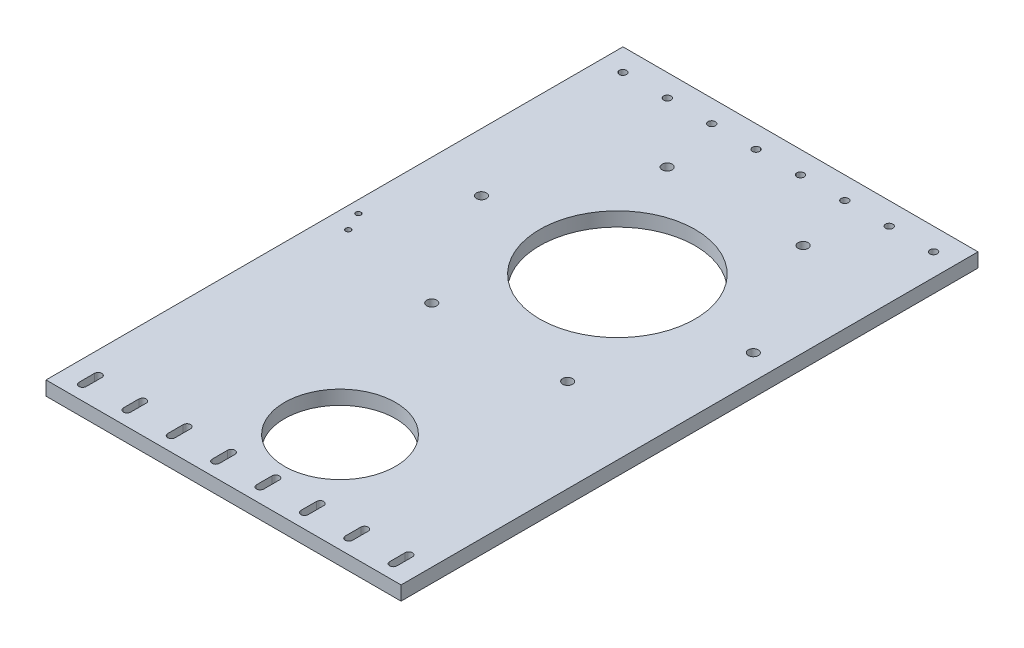
SolidWorks part; units mm, degrees
material "6061 Alloy"
ref_plane "Front Plane" through (0, 0, 0) normal (0, 0, 1) x (1, 0, 0)
ref_plane "Top Plane" through (0, 0, 0) normal (0, 1, 0) x (1, 0, 0)
ref_plane "Right Plane" through (0, 0, 0) normal (1, 0, 0) x (0, 0, -1)
sketch "Sketch1" plane through (0, 0, 0) normal (0, 1, 0) x (1, 0, 0)
  line L0 (87.5, 260) -> (87.5, 0) construction
  line L1 (0, 0) -> (160, 0)
  line L2 (0, 0) -> (0, 260)
  line L3 (0, 260) -> (160, 260)
  line L4 (160, 0) -> (160, 260)
  line L5 (87.5, 170) -> (148.75, 170) construction
  line L6 (10, 6.5) -> (10, 13.5) construction
  line L7 (5.4755, 135.2989) -> (9.5163, 126.7011) construction
  line L8 (22, 0) -> (22, 260) construction
  line L9 (22, 136) -> (0, 136) construction
  line L10 (22, 126) -> (0, 126) construction
  line L11 (0, 136) -> (0, 126) construction
  line L12 (17.3003, 136) -> (22, 126) construction
  line L13 (8.35, 6.5) -> (8.35, 13.5)
  line L14 (11.65, 6.5) -> (11.65, 13.5)
  line L15 (10, 250) -> (10, 0) construction
  line L16 (31.65, 6.5) -> (31.65, 13.5)
  line L17 (28.35, 6.5) -> (28.35, 13.5)
  line L18 (30, 6.5) -> (30, 13.5) construction
  line L19 (51.65, 6.5) -> (51.65, 13.5)
  line L20 (48.35, 6.5) -> (48.35, 13.5)
  line L21 (50, 6.5) -> (50, 13.5) construction
  line L22 (71.65, 6.5) -> (71.65, 13.5)
  line L23 (68.35, 6.5) -> (68.35, 13.5)
  line L24 (70, 6.5) -> (70, 13.5) construction
  line L25 (91.65, 6.5) -> (91.65, 13.5)
  line L26 (88.35, 6.5) -> (88.35, 13.5)
  line L27 (90, 6.5) -> (90, 13.5) construction
  line L28 (111.65, 6.5) -> (111.65, 13.5)
  line L29 (108.35, 6.5) -> (108.35, 13.5)
  line L30 (110, 6.5) -> (110, 13.5) construction
  line L31 (131.65, 6.5) -> (131.65, 13.5)
  line L32 (128.35, 6.5) -> (128.35, 13.5)
  line L33 (130, 6.5) -> (130, 13.5) construction
  line L34 (151.65, 6.5) -> (151.65, 13.5)
  line L35 (148.35, 6.5) -> (148.35, 13.5)
  line L36 (150, 6.5) -> (150, 13.5) construction
  line L37 (10, 250) -> (30, 250) construction
  circle A0 centre (87.5, 170) radius 35
  circle A1 centre (87.5, 45) radius 25
  circle A2 centre (87.5, 170) radius 61.25 construction
  circle A3 centre (148.75, 170) radius 2.25
  circle A4 centre (118.125, 116.9559) radius 2.25
  circle A5 centre (56.875, 116.9559) radius 2.25
  circle A6 centre (26.25, 170) radius 2.25
  circle A7 centre (56.875, 223.0441) radius 2.25
  circle A8 centre (118.125, 223.0441) radius 2.25
  circle A10 centre (5.4755, 135.2989) radius 1.175
  circle A11 centre (9.5163, 126.7011) radius 1.175
  circle A12 centre (87.5, 170) radius 78 construction
  circle A13 centre (10, 250) radius 1.65
  arc A14 (8.35, 6.5) -> (11.65, 6.5) centre (10, 6.5) ccw
  arc A15 (11.65, 13.5) -> (8.35, 13.5) centre (10, 13.5) ccw
  circle A16 centre (30, 250) radius 1.65
  arc A17 (28.35, 6.5) -> (31.65, 6.5) centre (30, 6.5) ccw
  arc A18 (31.65, 13.5) -> (28.35, 13.5) centre (30, 13.5) ccw
  circle A19 centre (50, 250) radius 1.65
  arc A20 (48.35, 6.5) -> (51.65, 6.5) centre (50, 6.5) ccw
  arc A21 (51.65, 13.5) -> (48.35, 13.5) centre (50, 13.5) ccw
  circle A22 centre (70, 250) radius 1.65
  arc A23 (68.35, 6.5) -> (71.65, 6.5) centre (70, 6.5) ccw
  arc A24 (71.65, 13.5) -> (68.35, 13.5) centre (70, 13.5) ccw
  circle A25 centre (90, 250) radius 1.65
  arc A26 (88.35, 6.5) -> (91.65, 6.5) centre (90, 6.5) ccw
  arc A27 (91.65, 13.5) -> (88.35, 13.5) centre (90, 13.5) ccw
  circle A28 centre (110, 250) radius 1.65
  arc A29 (108.35, 6.5) -> (111.65, 6.5) centre (110, 6.5) ccw
  arc A30 (111.65, 13.5) -> (108.35, 13.5) centre (110, 13.5) ccw
  circle A31 centre (130, 250) radius 1.65
  arc A32 (128.35, 6.5) -> (131.65, 6.5) centre (130, 6.5) ccw
  arc A33 (131.65, 13.5) -> (128.35, 13.5) centre (130, 13.5) ccw
  circle A34 centre (150, 250) radius 1.65
  arc A35 (148.35, 6.5) -> (151.65, 6.5) centre (150, 6.5) ccw
  arc A36 (151.65, 13.5) -> (148.35, 13.5) centre (150, 13.5) ccw
  point P15 (87.5, 170)
  point P29 (10, 10)
  point P42 (7.4959, 131)
  point P43 (0, 131)
  point P55 (30, 10)
  point P65 (50, 10)
  point P74 (70, 10)
  point P83 (90, 10)
  point P92 (110, 10)
  point P101 (130, 10)
  point P110 (150, 10)
  dimension "D3" = 70
  dimension "D4" = 50
  dimension "D7" = 122.5
  dimension "D8" = 4.5
  dimension "D11" = 124
  dimension "D13" = 2.35
  dimension "D16" = 156
  dimension "D19" = 3.3
  dimension "D24" = 240
  dimension "D1" = 160
  dimension "D2" = 260
  dimension "D5" = 125
  dimension "D6" = 90
  dimension "D10" = 61.25
  dimension "D12" = 65.5
  dimension "D14" = 9.5
  dimension "D15" = 10
  dimension "D17" = 11
  dimension "D18" = 72.5
  dimension "D20" = 10
  dimension "D21" = 10
  dimension "D22" = 3.3
  dimension "D23" = 7
  dimension "D26" = 20
  dimension "D25" = 8
  dimension "D9" = 6
extrude "Boss-Extrude1" add sketch "Sketch1" along normal blind 6.35 contours A1 | A0 | A4 | A8 | A7 | A6 | L4 L3 L2 L1 | A3 | A5 | A11 | A10 | A28 | A25 | A31 | A34 | A22 | A19 | A16 | A13 | L14 A15 L13 A14 | L16 A18 L17 A17 | L19 A21 L20 A20 | L22 A24 L23 A23 | L25 A27 L26 A26 | L28 A30 L29 A29 | L31 A33 L32 A32 | L34 A36 L35 A35 region at (87.5, 0, -170) region at (87.5, 0, -45) region at (118.125, 0, -116.9559) region at (26.25, 0, -170) region at (56.875, 0, -223.0441) region at (118.125, 0, -223.0441)
